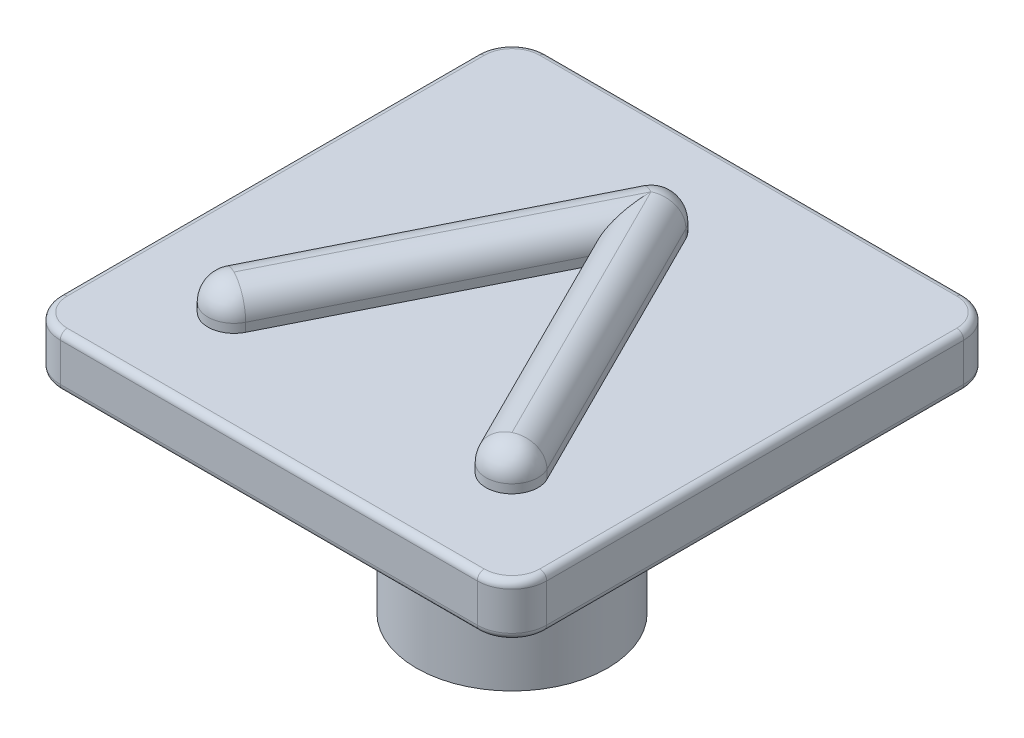
SolidWorks part; units mm, degrees
ref_plane "Front Plane" through (0, 0, 0) normal (0, 0, 1) x (1, 0, 0)
ref_plane "Top Plane" through (0, 0, 0) normal (0, 1, 0) x (1, 0, 0)
ref_plane "Right Plane" through (0, 0, 0) normal (1, 0, 0) x (0, 0, -1)
sketch "Sketch1" plane through (0, 0, 0) normal (0, 1, 0) x (1, 0, 0)
  line L1 (-7.3247, 4.3967) -> (4.6753, 4.3967)
  line L2 (-8.3247, 3.3967) -> (-8.3247, -8.6033)
  line L3 (-7.3247, -9.6033) -> (4.6753, -9.6033)
  line L4 (5.6753, 3.3967) -> (5.6753, -8.6033)
  arc A0 (-8.3247, -8.6033) -> (-7.3247, -9.6033) centre (-7.3247, -8.6033) ccw
  arc A1 (4.6753, -9.6033) -> (5.6753, -8.6033) centre (4.6753, -8.6033) ccw
  arc A2 (4.6753, 4.3967) -> (5.6753, 3.3967) centre (4.6753, 3.3967) cw
  arc A3 (-7.3247, 4.3967) -> (-8.3247, 3.3967) centre (-7.3247, 3.3967) ccw
  point P8 (5.6753, -9.6033)
  point P11 (5.6753, 4.3967)
  point P14 (-8.3247, 4.3967)
  dimension "D3" = 1
  dimension "D1" = 14
  dimension "D2" = 14
extrude "Boss-Extrude1" add sketch "Sketch1" along normal blind 1.5
sketch "Sketch2" plane through (0, 0, 0) normal (0, -1, 0) x (1, 0, 0)
  line L0 (-7.3247, 9.6033) -> (4.6753, 9.6033) construction
  line L1 (5.6753, 8.6033) -> (5.6753, -3.3967) construction
  line L2 (-1.3247, -4.3967) -> (-1.3247, 9.6033) construction
  line L3 (-8.3247, 2.6033) -> (5.6753, 2.6033) construction
  line L4 (-8.3247, -3.3967) -> (-8.3247, 8.6033) construction
  circle A0 centre (-1.3247, 2.6033) radius 2.75
  dimension "D1" = 7
  dimension "D2" = 7
extrude "Boss-Extrude2" add sketch "Sketch2" along normal blind 6
sketch "Sketch3" plane through (0, -6, 0) normal (0, -1, 0) x (1, 0, 0)
  line L0 (-1.3247, 5.3533) -> (-1.3247, -0.1467) construction
  line L1 (-3.3247, 3.1533) -> (0.6753, 3.1533)
  line L2 (-3.3247, 3.1533) -> (-3.3247, 2.0533)
  line L3 (-3.3247, 2.0533) -> (0.6753, 2.0533)
  line L4 (0.6753, 3.1533) -> (0.6753, 2.0533)
  line L5 (-1.8747, 4.6033) -> (-0.7747, 4.6033)
  line L6 (-1.8747, 4.6033) -> (-1.8747, 0.6033)
  line L7 (-1.8747, 0.6033) -> (-0.7747, 0.6033)
  line L8 (-0.7747, 4.6033) -> (-0.7747, 0.6033)
  line L9 (-4.0747, 2.6033) -> (1.4253, 2.6033) construction
  circle A3 centre (-1.3247, 2.6033) radius 2.75 construction
  circle A4 centre (-1.3247, 2.6033) radius 2.75 construction
  dimension "D7" = 0.55
  dimension "D1" = 4
  dimension "D2" = 1.1
  dimension "D3" = 1.1
  dimension "D4" = 4
  dimension "D8" = 0.55
extrude "Cut-Extrude1" cut sketch "Sketch3" against normal blind 6 contours L8 L5 L6 L1 | L1 L8 L3 L4 | L8 L1 L6 L3 | L6 L1 L2 L3 | L8 L3 L6 L7 region at (-2.5997, -6, 2.6033) region at (-1.3247, -6, 3.8783) region at (-1.3247, -6, 2.6033) region at (-0.0497, -6, 2.6033) region at (-1.3247, -6, 1.3283)
chamfer "Chamfer1" distance 0.3 angle 45 12 edges at (-1.3247, -6, 0.6033) (-1.8747, -6, 1.3283) (-2.5997, -6, 2.0533) (-3.3247, -6, 2.6033) (-2.5997, -6, 3.1533) (-0.7747, -6, 1.3283) (-0.0497, -6, 2.0533) (0.6753, -6, 2.6033) (-0.0497, -6, 3.1533) (-0.7747, -6, 3.8783) (-1.3247, -6, 4.6033) (-1.8747, -6, 3.8783)
fillet "Fillet1" radius 1 1 edges at (-1.3247, 0, -0.1467)
sketch "Sketch4" plane through (0, 1.5, 0) normal (0, 1, 0) x (1, 0, 0)
  line L0 (-1.3247, 4.3967) -> (-1.3247, -9.6033) construction
  line L1 (4.6753, 4.3967) -> (-7.3247, 4.3967) construction
  line L2 (-7.3247, -9.6033) -> (4.6753, -9.6033) construction
  line L3 (5.6753, -2.6033) -> (-8.3247, -2.6033) construction
  line L4 (-8.3247, 3.3967) -> (-8.3247, -8.6033) construction
  line L5 (5.6753, -8.6033) -> (5.6753, 3.3967) construction
  line L6 (-5.3247, 4.3967) -> (-5.3247, -9.6033) construction
  line L7 (2.6753, 4.3967) -> (2.6753, -9.6033) construction
  line L8 (-8.3247, 1.3967) -> (5.6753, 1.3967) construction
  line L9 (5.6753, -6.6033) -> (-8.3247, -6.6033) construction
  line L10 (-1.3247, 1.3967) -> (-5.3247, -6.6033) construction
  line L11 (-0.6539, 1.0613) -> (-4.6539, -6.9387)
  line L12 (-1.9955, 1.7321) -> (-5.9955, -6.2679)
  line L13 (-1.3247, 1.3967) -> (2.6753, -6.6033) construction
  line L14 (-0.6539, 1.7321) -> (3.3461, -6.2679)
  line L15 (-1.9955, 1.0613) -> (2.0045, -6.9387)
  arc A0 (-0.6539, 1.0613) -> (-1.9955, 1.7321) centre (-1.3247, 1.3967) ccw
  arc A1 (-5.9955, -6.2679) -> (-4.6539, -6.9387) centre (-5.3247, -6.6033) ccw
  arc A2 (-0.6539, 1.7321) -> (-1.9955, 1.0613) centre (-1.3247, 1.3967) ccw
  arc A3 (2.0045, -6.9387) -> (3.3461, -6.2679) centre (2.6753, -6.6033) ccw
  point P14 (-3.3247, -2.6033)
  point P19 (0.6753, -2.6033)
  dimension "D1" = 4
  dimension "D2" = 4
  dimension "D3" = 4
  dimension "D4" = 4
fillet "Fillet3" radius 0.2 16 edges at (5.3824, 1.5, -4.1038) (5.6753, 1.5, 2.6033) (5.3824, 1.5, 9.3104) (-1.3247, 1.5, 9.6033) (-8.0318, 1.5, 9.3104) (-8.0318, 1.5, -4.1038) (-8.3247, 1.5, 2.6033) (-1.3247, 1.5, -4.3967) (5.3824, 0, 9.3104) (5.6753, 0, 2.6033) (5.3824, 0, -4.1038) (-1.3247, 0, -4.3967) (-8.0318, 0, -4.1038) (-8.3247, 0, 2.6033) (-8.0318, 0, 9.3104) (-1.3247, 0, 9.6033)
extrude "Boss-Extrude3" add sketch "Sketch4" along normal blind 1 contours L15 A3 L14 A0 L11 | A0 A2 L15 L11 | A2 L12 A1 L11 L15 region at (1.0268, 1.5, 3.2672) region at (-1.3247, 1.5, -1.175) region at (-3.6761, 1.5, 3.2672)
fillet "Fillet6" radius 0.75 7 edges at (-5.6601, 2.5, 7.2741) (-2.9893, 2.5, 3.6095) (0.3399, 2.5, 3.6095) (3.0107, 2.5, 7.2741) (1.3461, 2.5, 2.2679) (-1.3247, 2.5, -2.1467) (-3.9955, 2.5, 2.2679)
